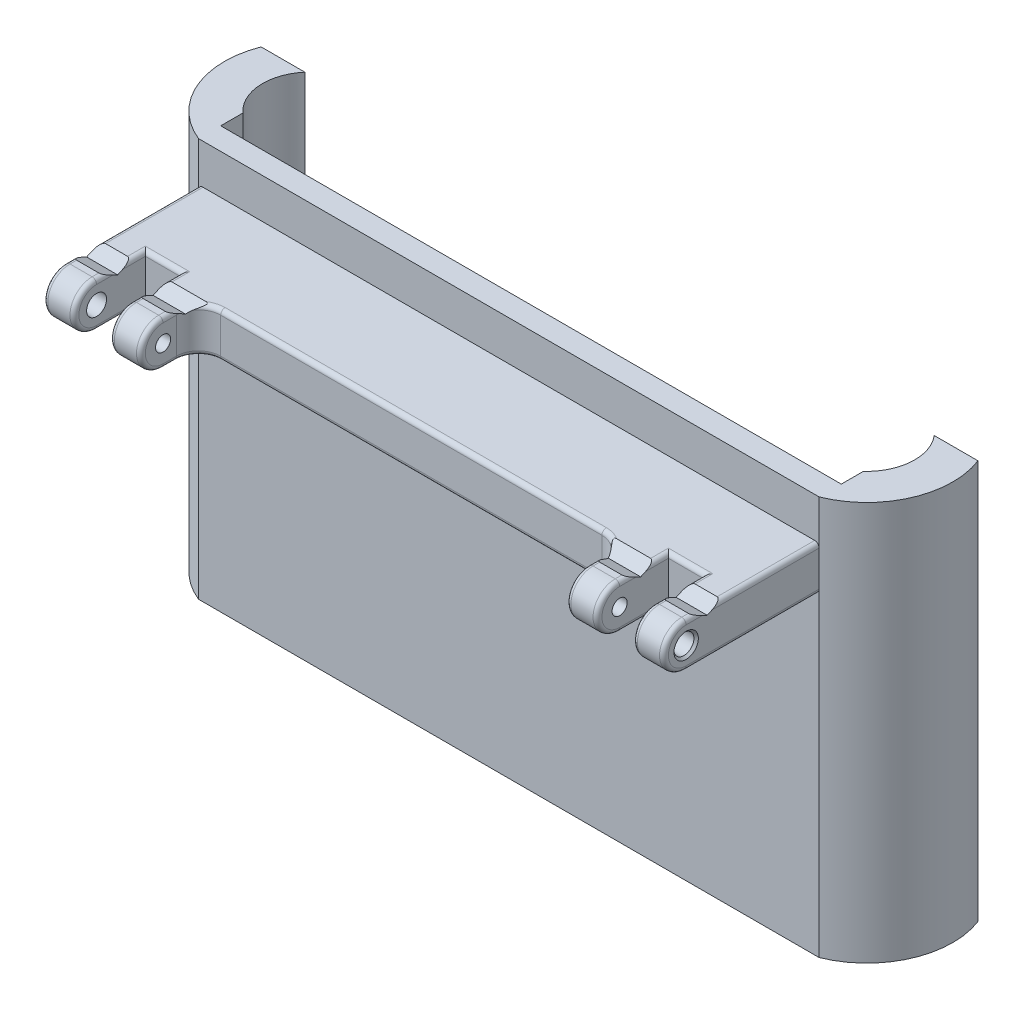
SolidWorks part; units mm, degrees
ref_plane "Plan de face" through (0, 0, 0) normal (0, 0, 1) x (1, 0, 0)
ref_plane "Plan de dessus" through (0, 0, 0) normal (0, 1, 0) x (1, 0, 0)
ref_plane "Plan de droite" through (0, 0, 0) normal (1, 0, 0) x (0, 0, -1)
sketch "Esquisse1" plane through (0, 0, 0) normal (0, 1, 0) x (1, 0, 0)
  line L0 (73.45, 0) -> (-73.45, 0) construction
  line L1 (0, 0) -> (0, 12.2652) construction
  line L6 (0, -8.1066) -> (-67.75, -8.1066) construction
  line L7 (-62.6, 12.2652) -> (0, 12.2652) construction
  line L8 (-70, -6.5386) -> (70, -6.5386) construction
  line L9 (-71, 8.436) -> (71, 8.436) construction
  line L11 (-70, -6.5386) -> (-70, -11.5386)
  line L13 (70, -6.5386) -> (70, -11.5386)
  line L14 (71, 8.436) -> (80.8652, 8.436)
  line L15 (70, -11.5386) -> (-70, -11.5386)
  line L16 (70, -11.5386) -> (70, -16.5386) construction
  line L17 (70, -16.5386) -> (-70, -16.5386)
  line L18 (-70, -11.5386) -> (-70, -16.5386) construction
  line L19 (-71, 8.436) -> (-80.8652, 8.436)
  arc A0 (-62.6, 12.2652) -> (-67.75, -8.1066) centre (-62.75, 1.4663) ccw construction
  arc A1 (80.8652, 8.436) -> (70, -16.5386) centre (62.75, 1.4663) cw
  arc A2 (62.6, 12.2652) -> (67.75, -8.1066) centre (62.75, 1.4663) cw construction
  arc A3 (71, 8.436) -> (70, -6.5386) centre (62.75, 1.4663) cw
  arc A4 (-71, 8.436) -> (-70, -6.5386) centre (-62.75, 1.4663) ccw
  arc A5 (-80.8652, 8.436) -> (-70, -16.5386) centre (-62.75, 1.4663) ccw
  point P4 (0, 0)
  dimension "D2" = 10.8
  dimension "D6" = 140
  dimension "D1" = 146.9
  dimension "D3" = 67.75
  dimension "D4" = 62.6
  dimension "D5" = 62.75
  dimension "D7" = 5
  dimension "D8" = 142
  dimension "D9" = 5
extrude "Boss.-Extru.1" add sketch "Esquisse1" along normal blind 90 contours L19 A5 L17 A1 L14 A3 L13 L15 L11 A4 region at (-71.6621, 0, 9.0386)
ref_plane "Plan1" through (0, 71, 0) normal (0, -1, 0) x (-1, 0, 0)
sketch "Esquisse2" plane through (0, 71, 0) normal (0, -1, 0) x (-1, 0, 0)
  line L1 (-70, -16.5386) -> (70, -16.5386)
  line L2 (-70, -16.5386) -> (-70, -38.5386)
  line L3 (-70, -38.5386) -> (70, -38.5386)
  line L4 (70, -16.5386) -> (70, -38.5386)
  dimension "D1" = 22
extrude "Boss.-Extru.2" add sketch "Esquisse2" against normal blind 10
sketch "Esquisse3" plane through (-70, 0, 0) normal (-1, 0, 0) x (0, 0, 1)
  line L0 (38.5386, 81) -> (16.5386, 81) construction
  line L1 (38.5386, 71) -> (46.5386, 71)
  line L2 (38.5386, 71) -> (38.5386, 81)
  line L3 (38.5386, 81) -> (46.5386, 81)
  line L4 (46.5386, 71) -> (46.5386, 81) construction
  arc A0 (46.5386, 81) -> (46.5386, 71) centre (46.5386, 76) cw
  circle A1 centre (46.5386, 76) radius 1.7
  dimension "D1" = 8
  dimension "D2" = 3.4
extrude "Boss.-Extru.3" add sketch "Esquisse3" against normal up to surface (140 mm away) up to face at (70, 76, 27.5386)
sketch "Esquisse4" plane through (0, 81, 0) normal (0, 1, 0) x (1, 0, 0)
  line L0 (-63, -38.5386) -> (-70, -38.5386) construction
  line L1 (-63, -38.5386) -> (-55, -38.5386)
  line L2 (-63, -38.5386) -> (-63, -61.7649)
  line L3 (-63, -61.7649) -> (-55, -61.7649)
  line L4 (-55, -38.5386) -> (-55, -61.7649)
  line L5 (-48, -38.5386) -> (48, -38.5386)
  line L6 (-48, -38.5386) -> (-48, -61.7649)
  line L7 (-48, -61.7649) -> (48, -61.7649)
  line L8 (48, -38.5386) -> (48, -61.7649)
  line L9 (55, -38.5386) -> (63, -38.5386)
  line L10 (55, -38.5386) -> (55, -61.7649)
  line L11 (55, -61.7649) -> (63, -61.7649)
  line L12 (63, -38.5386) -> (63, -61.7649)
  line L13 (-70, -46.5386) -> (-70, -16.5386) construction
  line L14 (63, -38.5386) -> (70, -38.5386) construction
  line L15 (70, -16.5386) -> (70, -46.5386) construction
  line L16 (70, -16.5386) -> (-70, -16.5386) construction
  line L17 (0, -38.5386) -> (0, -16.5386) construction
  line L18 (-70, -16.5386) -> (70, -16.5386) construction
  line L19 (-48, -38.5386) -> (-55, -38.5386) construction
  line L20 (-63, -38.5386) -> (-55, -38.5386)
  line L21 (-63, -38.5386) -> (-63, -35.5386)
  line L22 (-55, -38.5386) -> (-55, -35.5386)
  line L23 (-63, -35.5386) -> (-55, -35.5386)
  line L24 (55, -38.5386) -> (63, -38.5386)
  line L25 (55, -38.5386) -> (55, -35.5386)
  line L26 (63, -38.5386) -> (63, -35.5386)
  line L27 (55, -35.5386) -> (63, -35.5386)
  line M20 (-70, -46.5386) -> (70, -46.5386)
  dimension "D1" = 8
  dimension "D2" = 7
  dimension "D3" = 22
  dimension "D4" = 7
  dimension "D5" = 3
extrude "Enlèv. mat.-Extru.1" cut sketch "Esquisse4" against normal blind 10 contours L4 L2 L3 M20 | L4 L1 L2 M20 | L23 L21 L1 L22 | L8 L5 L6 M20 | L8 L6 L7 M20 | L12 L10 L11 M20 | L12 L9 L10 M20 | L27 L25 L9 L26 region at (-59, 81, 37.0386) region at (-59, 81, 42.5386) region at (59, 81, 42.5386) region at (59, 81, 54.1517) region at (0, 81, 42.5386) region at (0, 81, 54.1517) region at (-59, 81, 54.1517) region at (59, 81, 37.0386)
sketch "Esquisse6" plane through (-70, 0, 0) normal (-1, 0, 0) x (0, 0, 1)
  circle A0 centre (46.5386, 76) radius 2.25
  dimension "D1" = 4.5
extrude "Enlèv. mat.-Extru.2" cut sketch "Esquisse6" against normal blind 10
mirror "Symétrie1" about plane through (0, 0, 0) normal (1, 0, 0) of "Enlèv. mat.-Extru.2"
chamfer "Chanfrein1" distance 0.5 angle 45 2 edges at (70, 76, 48.7886) (-70, 76, 48.7886)
fillet "Congé4" radius 5 2 edges at (48, 76, 38.5386) (-48, 76, 38.5386)
fillet "Congé1" radius 1 34 edges at (63, 71, 41.0386) (63, 76, 51.5386) (48, 71, 45.0386) (48, 76, 51.5386) (55, 71, 41.0386) (55, 76, 51.5386) (-63, 71, 41.0386) (-63, 76, 51.5386) (-55, 71, 41.0386) (-55, 76, 51.5386) (-48, 71, 45.0386) (-48, 76, 51.5386) (70, 71, 31.5386) (70, 76, 51.5386) (-70, 71, 31.5386) (-70, 76, 51.5386) (63, 81, 41.0386) (48, 81, 45.0386) (55, 81, 41.0386) (-63, 81, 41.0386) (-55, 81, 41.0386) (-48, 81, 45.0386) (0, 71, 38.5386) (0, 81, 38.5386) (70, 81, 31.5386) (-70, 81, 31.5386) (46.5355, 81, 40.003) (46.5355, 71, 40.003) (-46.5355, 71, 40.003) (-46.5355, 81, 40.003) (59, 71, 35.5386) (59, 81, 35.5386) (-59, 71, 35.5386) (-59, 81, 35.5386)
sketch "Esquisse8" plane through (-70, 0, 0) normal (-1, 0, 0) x (0, 0, 1)
  line L0 (45.0386, 81) -> (41.7886, 79.5)
  line L1 (16.5386, 81) -> (46.5386, 81) construction
  line L2 (41.7886, 79.5) -> (38.5386, 81)
  line L3 (41.7886, 79.5) -> (41.7886, 81) construction
  line L4 (38.5386, 81) -> (45.0386, 81)
  point P4 (41.8003, 79.5)
  dimension "D1" = 1.5
  dimension "D2" = 1.5
  dimension "D3" = 6.5
extrude "Enlèv. mat.-Extru.4" cut sketch "Esquisse8" against normal through all
equation "\"10K.8\"=29.8671"
